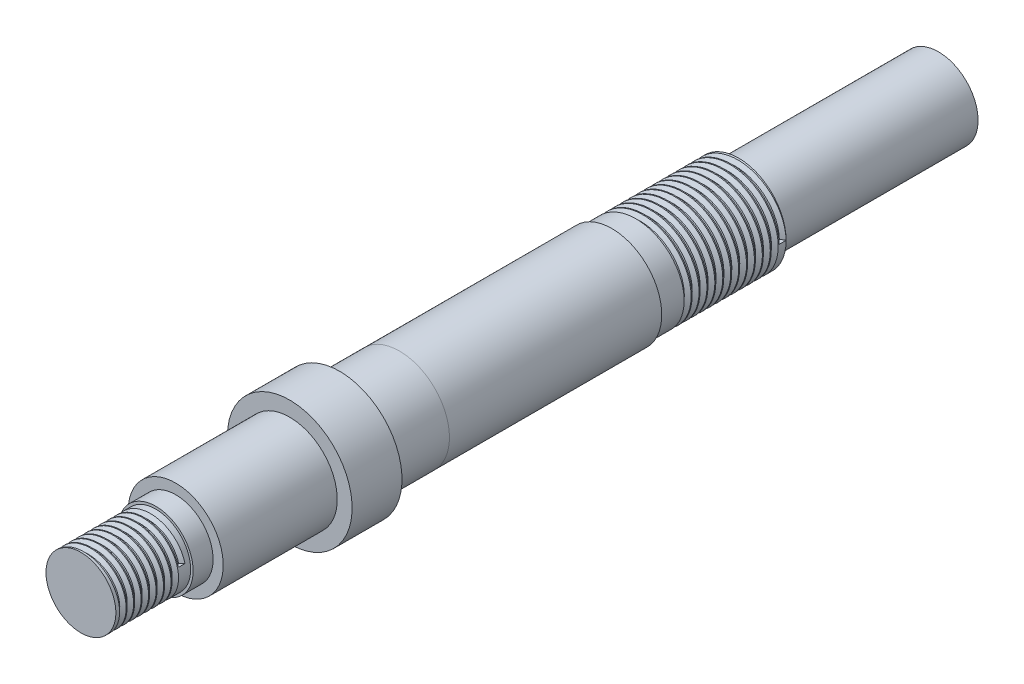
SolidWorks part; units mm, degrees
material "AISI 1020"
ref_plane "Front Plane" through (0, 0, 0) normal (0, 0, 1) x (1, 0, 0)
ref_plane "Top Plane" through (0, 0, 0) normal (0, 1, 0) x (1, 0, 0)
ref_plane "Right Plane" through (0, 0, 0) normal (1, 0, 0) x (0, 0, -1)
sketch "Derived Spindle Sketch" plane through (0, 0, 0) normal (1, 0, 0) x (0, 0, -1)
  line L0 (141.5523, 0) -> (-87.5573, 0)
  line L1 (93.1469, 36.5125) -> (0, 36.5125) construction
  line L2 (93.1469, 36.5125) -> (93.1469, -36.5125) construction
  line L3 (93.1469, -36.5125) -> (0, -36.5125) construction
  line L4 (0, 36.5125) -> (0, -36.5125) construction
  line L5 (0, 36.5125) -> (-15.24, 36.5125) construction
  line L6 (0, 36.5125) -> (0, -36.5125) construction
  line L7 (0, -36.5125) -> (-15.24, -36.5125) construction
  line L8 (-15.24, 36.5125) -> (-15.24, -36.5125) construction
  line L9 (-22.86, 9.525) -> (0, 9.525)
  line L10 (-22.86, 9.525) -> (-22.86, -9.525)
  line L11 (-22.86, -9.525) -> (0, -9.525)
  line L12 (0, 9.525) -> (0, -9.525)
  line L13 (22, 10.0076) -> (10, 10.0076)
  line L14 (22, 10.0076) -> (22, -10.0076)
  line L15 (22, -10.0076) -> (10, -10.0076)
  line L16 (10, 10.0076) -> (10, -10.0076)
  line L17 (64.5719, 9.9949) -> (52.5719, 9.9949)
  line L18 (64.5719, 9.9949) -> (64.5719, -9.9949)
  line L19 (64.5719, -9.9949) -> (52.5719, -9.9949)
  line L20 (52.5719, 9.9949) -> (52.5719, -9.9949)
  line L22 (52.5719, 9.9949) -> (22, 9.9949)
  line L23 (52.5719, 9.9949) -> (52.5719, -9.9949)
  line L24 (52.5719, -9.9949) -> (22, -9.9949)
  line L25 (22, 9.9949) -> (22, -9.9949)
  line L26 (64.5719, 9.525) -> (89.9719, 9.525)
  line L27 (64.5719, 9.525) -> (64.5719, -9.525)
  line L28 (64.5719, -9.525) -> (89.9719, -9.525)
  line L29 (89.9719, 9.525) -> (89.9719, -9.525)
  line L30 (115.1417, 7.9375) -> (130.0369, 7.9375)
  line L31 (115.1417, 7.9375) -> (115.1417, -7.9375)
  line L32 (115.1417, -7.9375) -> (130.0369, -7.9375)
  line L33 (130.0369, 7.9375) -> (130.0369, -7.9375)
  line L34 (10, 12.5) -> (0, 12.5)
  line L35 (10, 12.5) -> (10, -12.5)
  line L36 (10, -12.5) -> (0, -12.5)
  line L37 (0, 12.5) -> (0, -12.5)
  line L38 (-41.86, 7.0002) -> (-26.86, 7.0002)
  line L39 (-41.86, 7.0002) -> (-41.86, -7.0002)
  line L40 (-41.86, -7.0002) -> (-26.86, -7.0002)
  line L41 (-26.86, 7.0002) -> (-26.86, -7.0002)
  line L42 (93.1469, 36.5125) -> (102.0369, 36.5125) construction
  line L43 (93.1469, 36.5125) -> (93.1469, -36.5125) construction
  line L44 (93.1469, -36.5125) -> (102.0369, -36.5125) construction
  line L45 (102.0369, 36.5125) -> (102.0369, -36.5125) construction
  line L46 (115.1417, -7.9375) -> (89.9719, -7.9375)
  line L47 (115.1417, -7.9375) -> (115.1417, 7.9375)
  line L48 (115.1417, 7.9375) -> (89.9719, 7.9375)
  line L49 (89.9719, -7.9375) -> (89.9719, 7.9375)
  line L54 (-22.86, 7.5) -> (-26.86, 7.5)
  line L55 (-22.86, 7.5) -> (-22.86, -7.5)
  line L56 (-22.86, -7.5) -> (-26.86, -7.5)
  line L57 (-26.86, 7.5) -> (-26.86, -7.5)
revolve "Shaft Revolve" add sketch "Derived Spindle Sketch" angle 360 about L0 region at (0, 3.9687, -122.5893) region at (0, 3.9687, -102.5568) region at (0, 4.7625, -77.2719) region at (0, 4.9975, -58.5719) region at (0, 4.9975, -37.2859) region at (0, 5.0038, -16) region at (0, 6.25, -5) region at (0, 4.7625, 11.43) region at (0, 3.75, 24.86) region at (0, 3.5001, 34.36)
thread "M14x1 thread" pitch 1.5 method cut profile "Thread Profile1" start angle 0, offset 0, length 12.7, pitch 1.5, diameter 14.0005
ref_plane "Plane1" through (-7.0002, 0, 41.86) normal (0, -1, 0) x (-1, 0, 0)
sketch "Thread Profile1" plane through (-7.0002, 0, 41.86) normal (0, -1, 0) x (-1, 0, 0)
  line L0 (0, 0) -> (0, 1.5) construction
  line L11 (0, 0) -> (0, 1.3125)
  line L12 (0, 1.3125) -> (-0.8119, 0.8437)
  line L13 (-0.8119, 0.8437) -> (-0.8119, 0.4687)
  line L15 (-0.8119, 0.4687) -> (0, 0)
  line L17 (-0.8119, 0.6562) -> (0, 0.6562) construction
  point P2 (0, 0)
  dimension "Pitch" = 1.5
  dimension "Profile_Angle" = 60
  dimension "Profile_Land" = 0.375
  dimension "Profile_Height" = 0.8119
thread "3/4-16 thread" pitch 1.5875 method cut profile "Thread Profile2" start angle 0, offset 0, length 20.32, pitch 1.5875, diameter 19.05
ref_plane "Plane2" through (9.525, 0, -89.9719) normal (0, -1, 0) x (1, 0, 0)
sketch "Thread Profile2" plane through (9.525, 0, -89.9719) normal (0, -1, 0) x (1, 0, 0)
  line L0 (0, 0) -> (0, 1.5875) construction
  line L11 (0, 0) -> (0, 1.3891)
  line L12 (0, 1.3891) -> (-0.8593, 0.893)
  line L13 (-0.8593, 0.893) -> (-0.8593, 0.4961)
  line L15 (-0.8593, 0.4961) -> (0, 0)
  line L17 (-0.8593, 0.6945) -> (0, 0.6945) construction
  point P2 (0, 0)
  dimension "Pitch" = 1.5875
  dimension "Profile_Angle" = 60
  dimension "Profile_Land" = 0.3969
  dimension "Profile_Height" = 0.8593
